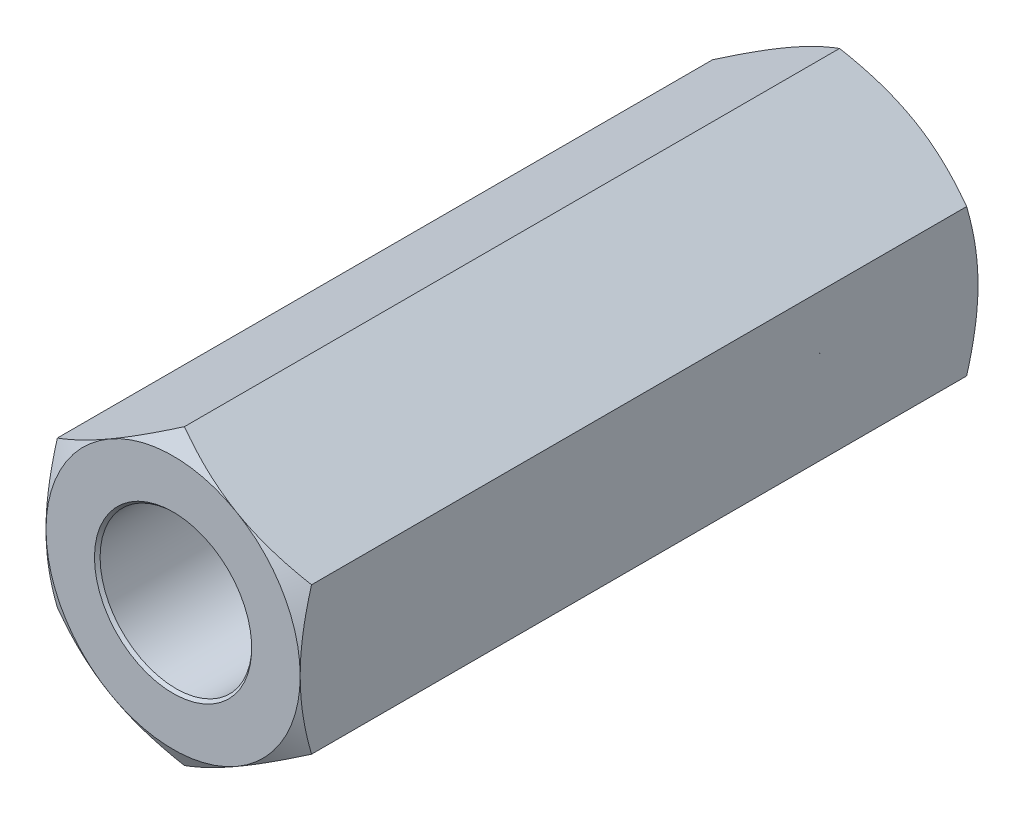
SolidWorks part; units mm, degrees
ref_plane "Front Plane" through (0, 0, 0) normal (0, 0, 1) x (1, 0, 0)
ref_plane "Top Plane" through (0, 0, 0) normal (0, 1, 0) x (1, 0, 0)
ref_plane "Right Plane" through (0, 0, 0) normal (1, 0, 0) x (0, 0, -1)
sketch "Sketch3" plane through (0, 0, 0) normal (1, 0, 0) x (0, 0, -1)
  line L0 (-6.35, 0) -> (6.35, 0) construction
  line L1 (0, 2.3813) -> (0, -2.3813) construction
  line L2 (-6.35, 1.4224) -> (-6.35, -1.4224) construction
  point P2 (1.5875, 0)
  point P3 (-1.5875, 0)
  dimension "D1" = 4.7625
  dimension "Length" = 12.7
  dimension "Min Thread Length" = 4.7625
  dimension "Thread Dia" = 2.8448
  dimension "Hex" = 4.7625
sketch "Sketch1" plane through (0, 0, 0) normal (0, 0, 1) x (1, 0, 0)
  line L1 (0, 2.7496) -> (-2.3813, 1.3748)
  line L2 (-2.3813, 1.3748) -> (-2.3813, -1.3748)
  line L3 (-2.3813, -1.3748) -> (0, -2.7496)
  line L4 (0, -2.7496) -> (2.3813, -1.3748)
  line L5 (2.3813, -1.3748) -> (2.3813, 1.3748)
  line L6 (2.3813, 1.3748) -> (0, 2.7496)
  circle A0 centre (0, 0) radius 2.3813 construction
  circle A1 centre (0, 0) radius 1.4224
extrude "Extrude1" add sketch "Sketch1" along normal up to vertex (6.35 mm away) and the other way up to vertex (6.35 mm away) up to point (0, 0, 6.35) other way up to point (0, 0, -6.35)
sketch "Sketch11" plane through (0, 0, -6.35) normal (0, 0, -1) x (-1, 0, 0)
  circle A0 centre (0, 0) radius 1.4224 construction
  circle A1 centre (0, 0) radius 1.4224
curve "Helix/Spiral1" pitch 0.635 height 13.335 turns 21 parameters "Pitch"=0.635
sketch "Sketch12" plane through (0, 0, 0) normal (1, 0, 0) x (0, 0, -1)
  line L0 (6.9056, 1.4224) -> (6.35, 1.4224)
  line L1 (6.9056, 1.4224) -> (6.6675, 1.01)
  line L2 (6.6675, 1.01) -> (6.5881, 1.01)
  line L3 (6.5881, 1.01) -> (6.35, 1.4224)
  line L4 (6.6278, 1.01) -> (6.6278, 1.4224) construction
  line L5 (6.7866, 1.2162) -> (6.4691, 1.2162) construction
  dimension "D1" = 0.0794
  dimension "D2" = 0.3175
  dimension "D3" = 60
sweep "Sweep1" [suppressed] add profiles "Sketch12" path "Helix/Spiral1"
sketch "Sketch6" plane through (0, 0, -6.35) normal (0, 0, -1) x (-1, 0, 0)
  line L6 (0, 2.7496) -> (-2.3813, 1.3748)
  line L7 (-2.3813, 1.3748) -> (-2.3813, -1.3748)
  line L8 (-2.3813, -1.3748) -> (0, -2.7496)
  line L9 (0, -2.7496) -> (2.3813, -1.3748)
  line L10 (2.3813, -1.3748) -> (2.3813, 1.3748)
  line L11 (2.3813, 1.3748) -> (0, 2.7496)
  line L12 (0, 2.7496) -> (-2.3813, 1.3748)
  line L13 (-2.3813, 1.3748) -> (-2.3813, -1.3748)
  line L14 (-2.3813, -1.3748) -> (0, -2.7496)
  line L15 (0, -2.7496) -> (2.3813, -1.3748)
  line L16 (2.3813, -1.3748) -> (2.3813, 1.3748)
  line L17 (2.3813, 1.3748) -> (0, 2.7496)
  dimension "D1" = 0
extrude "Extrude2" [suppressed] cut sketch "Sketch6" along normal through all
sketch "Sketch7" plane through (0, 0, -6.35) normal (0, 0, -1) x (-1, 0, 0)
  circle A2 centre (0, 0) radius 1.4732
  circle A3 centre (0, 0) radius 1.4732
  dimension "D1" = 0.0508
extrude "Extrude3" cut sketch "Sketch7" against normal through all draft 43
sketch "Sketch8" plane through (0, 0, -6.35) normal (0, 0, -1) x (-1, 0, 0)
  circle A0 centre (0, 0) radius 2.3813 construction
  circle A1 centre (0, 0) radius 2.3813
extrude "Extrude4" cut sketch "Sketch8" against normal through all draft 60 flip side to cut
mirror "Mirror1" about plane through (0, 0, 0) normal (0, 0, 1) of "Extrude2", "Extrude3", "Extrude4"
sketch "Sketch9" [suppressed] plane through (0, 0, 0) normal (1, 0, 0) x (0, 0, -1)
  line L1 (-1.5875, 0.8128) -> (1.5875, 0.8128)
  line L2 (-1.5875, 0.8128) -> (-1.5875, 0)
  line L3 (-1.5875, 0) -> (1.5875, 0)
  line L4 (1.5875, 0.8128) -> (1.5875, 0)
  line L7 (-6.35, 0) -> (6.35, 0) construction
revolve "Revolve" [suppressed] add sketch "Sketch9" angle 360 about L0
sketch "Sketch10" [suppressed] plane through (0, 0, 0) normal (1, 0, 0) x (0, 0, -1)
  line L0 (6.35, 0.762) -> (1.5875, 0.762)
  line L1 (-6.35, 0.762) -> (-1.5875, 0.762)
  line L2 (1.5875, 0.762) -> (1.5875, -0.762)
  line L3 (-6.35, -0.8128) -> (-1.5875, -0.8128)
  line L4 (-1.5875, 0.762) -> (-1.5875, -0.8128)
  line L5 (1.5875, -0.762) -> (6.35, -0.762)
equation "\"D1@Sketch3\" = \"Min Thread Length@Sketch3\""
equation "\"D3@Helix/Spiral1\" = \"Length@Sketch3\"+\"Pitch@Helix/Spiral1\""
equation "\"D1@Sketch12\" = \"Pitch@Helix/Spiral1\"*.125"
equation "\"D2@Sketch12\" = \"Pitch@Helix/Spiral1\"*.5"
